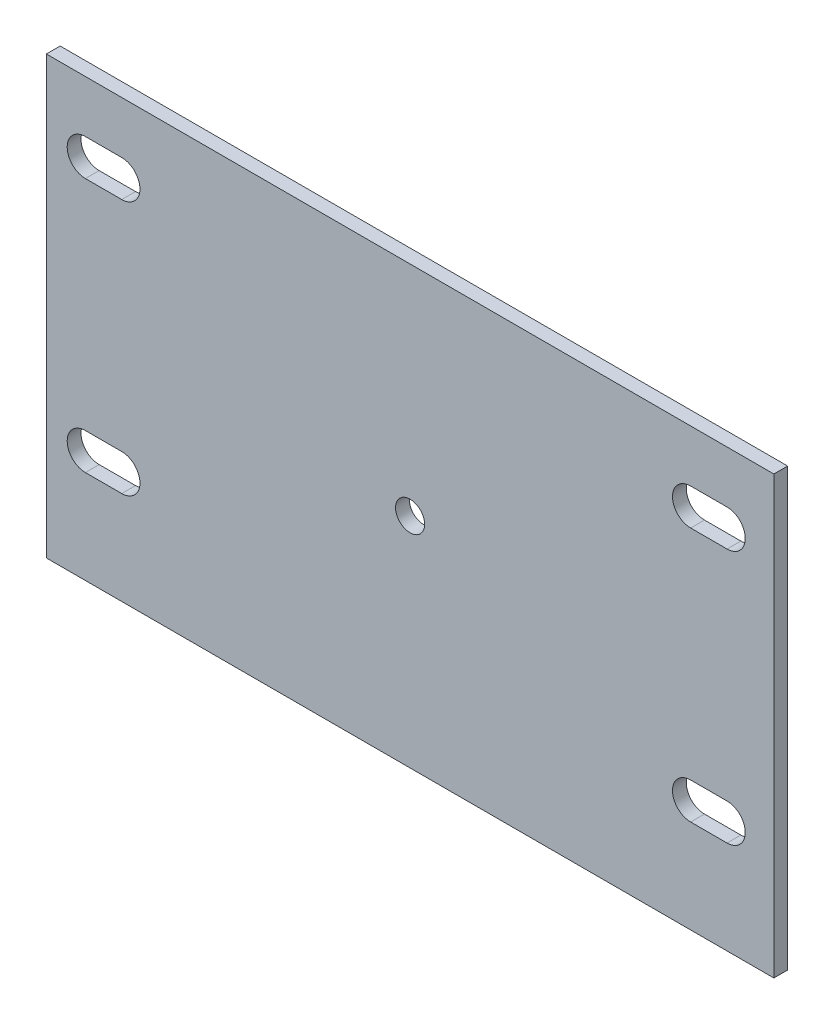
SolidWorks part; units mm, degrees
ref_plane "Front Plane" through (0, 0, 0) normal (0, 0, 1) x (1, 0, 0)
ref_plane "Top Plane" through (0, 0, 0) normal (0, 1, 0) x (1, 0, 0)
ref_plane "Right Plane" through (0, 0, 0) normal (1, 0, 0) x (0, 0, -1)
sketch "Sketch1" plane through (0, 0, 0) normal (0, 0, 1) x (1, 0, 0)
  line L1 (-66.0087, 33.0867) -> (33.9913, 33.0867)
  line L2 (-66.0087, 33.0867) -> (-66.0087, -26.9133)
  line L3 (-66.0087, -26.9133) -> (33.9913, -26.9133)
  line L4 (33.9913, 33.0867) -> (33.9913, -26.9133)
  dimension "D1" = 100
  dimension "D2" = 60
base flange "Base-Flange1" sketch "Sketch1" thickness 1.8974 reverse thickness direction no parameters "D1"=2.54
sketch "Sketch6" plane through (0, 0, 0) normal (0, 0, 1) x (1, 0, 0)
  line L0 (33.9913, 33.0867) -> (-66.0087, 33.0867) construction
  line L1 (-66.0087, 33.0867) -> (-66.0087, -26.9133) construction
  circle A0 centre (-58.1444, 23.4388) radius 2.5
  circle A1 centre (-58.1444, -11.5612) radius 2.5
  circle A2 centre (25.0609, 23.4388) radius 2.5
  circle A3 centre (25.0609, -11.5612) radius 2.5
  circle A4 centre (-16.0087, 3.0867) radius 2
  point P12 (-16.0087, 33.0867)
  point P13 (-66.0087, 3.0867)
  dimension "D1" = 5
sketch "Sketch7" plane through (0, 0, 0) normal (0, 0, 1) x (1, 0, 0)
  line L0 (-60.6444, -11.5612) -> (-55.6444, -11.5612) construction
  line L1 (-60.6444, -9.0612) -> (-55.6444, -9.0612)
  line L2 (-60.6444, -14.0612) -> (-55.6444, -14.0612)
  line L3 (-60.6444, 23.4388) -> (-55.6444, 23.4388) construction
  line L4 (-60.6444, 25.9388) -> (-55.6444, 25.9388)
  line L5 (-60.6444, 20.9388) -> (-55.6444, 20.9388)
  line L6 (27.5609, 23.4388) -> (22.5609, 23.4388) construction
  line L7 (27.5609, 20.9388) -> (22.5609, 20.9388)
  line L8 (27.5609, 25.9388) -> (22.5609, 25.9388)
  line L9 (27.5609, -11.5612) -> (22.5609, -11.5612) construction
  line L10 (27.5609, -14.0612) -> (22.5609, -14.0612)
  line L11 (27.5609, -9.0612) -> (22.5609, -9.0612)
  arc A0 (-60.6444, -9.0612) -> (-60.6444, -14.0612) centre (-60.6444, -11.5612) ccw
  arc A1 (-55.6444, -14.0612) -> (-55.6444, -9.0612) centre (-55.6444, -11.5612) ccw
  arc A2 (-60.6444, 25.9388) -> (-60.6444, 20.9388) centre (-60.6444, 23.4388) ccw
  arc A3 (-55.6444, 20.9388) -> (-55.6444, 25.9388) centre (-55.6444, 23.4388) ccw
  arc A4 (27.5609, 20.9388) -> (27.5609, 25.9388) centre (27.5609, 23.4388) ccw
  arc A5 (22.5609, 25.9388) -> (22.5609, 20.9388) centre (22.5609, 23.4388) ccw
  arc A6 (27.5609, -14.0612) -> (27.5609, -9.0612) centre (27.5609, -11.5612) ccw
  arc A7 (22.5609, -9.0612) -> (22.5609, -14.0612) centre (22.5609, -11.5612) ccw
  circle A9 centre (-16.0087, 3.0867) radius 2
  point P3 (-58.1444, -11.5612)
  point P8 (-58.1444, 23.4388)
  point P16 (25.0609, 23.4388)
  point P24 (25.0609, -11.5612)
extrude "Cut-Extrude2" cut sketch "Sketch7" against normal blind 2 normal cut yes
sketch "Bend-Lines1" plane through (0, 0, 0) normal (0, 1, 0) x (1, 0, 0)
sketch "Bounding-Box1" plane through (0, 0, 0) normal (0, 1, 0) x (1, 0, 0)
sheet metal parameters "Sheet-Metal1" thickness 1.8974 parameters "D1"=2.54
flat pattern "Flat-Pattern1" [suppressed]
sketch "Bend-Lines2" plane through (0, 0, 0) normal (0, 1, 0) x (1, 0, 0)
sketch "Bounding-Box2" [suppressed] plane through (0, 0, 0) normal (0, 1, 0) x (1, 0, 0)
sheet metal parameters "Sheet-Metal3" thickness 1.8974 parameters "D1"=2.54
flat pattern "Flat-Pattern1"
sketch "Bend-Lines2" plane through (0, 0, 0) normal (0, 1, 0) x (1, 0, 0)
sketch "Bounding-Box2" [suppressed] plane through (0, 0, 0) normal (0, 1, 0) x (1, 0, 0)
